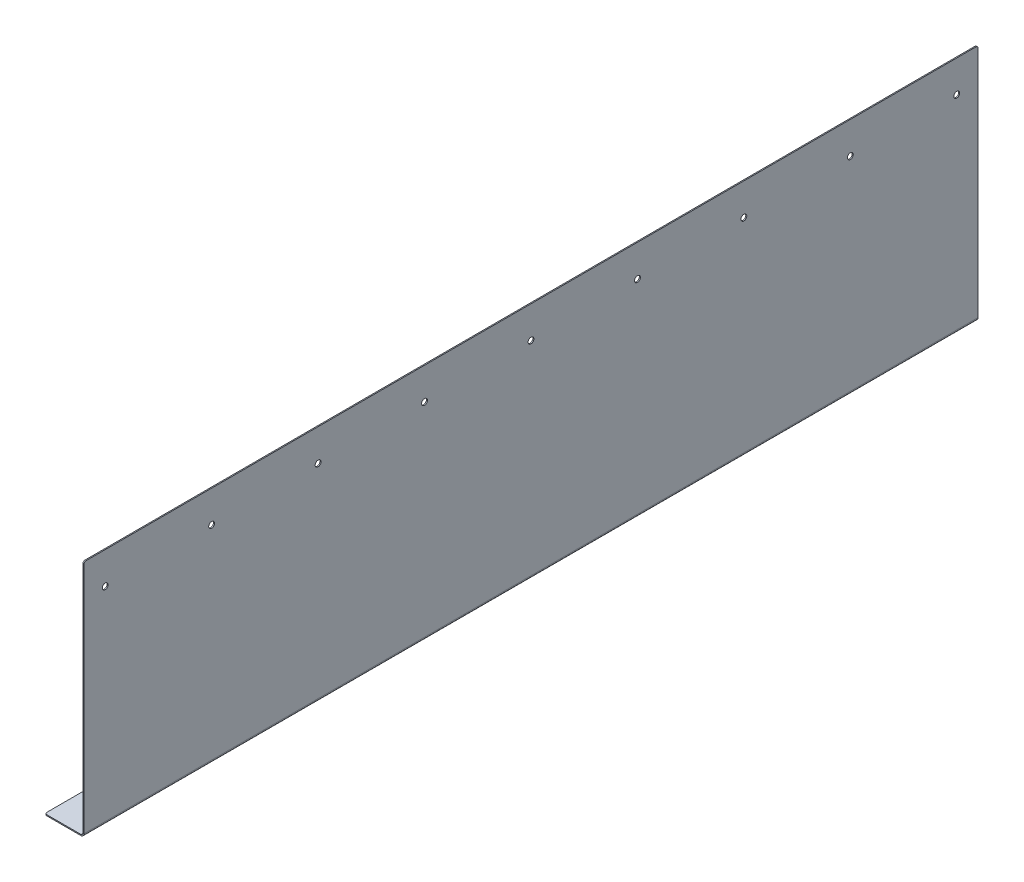
SolidWorks part; units mm, degrees
note: The reader was unsure of these and kept them because the rebuilt part matched: flange length of "Edge-Flange1".
material "3.3547 (EN-AW 5083)"
ref_plane "Front Plane" through (0, 0, 0) normal (0, 0, 1) x (1, 0, 0)
ref_plane "Top Plane" through (0, 0, 0) normal (0, 1, 0) x (1, 0, 0)
ref_plane "Right Plane" through (0, 0, 0) normal (1, 0, 0) x (0, 0, -1)
sketch "Sketch2" plane through (0, 0, 0) normal (0, 0, 1) x (1, 0, 0)
  line L0 (0, 0) -> (0, 225)
  dimension "D1" = 225
base flange "Base-Flange1" sketch "Sketch2" end condition mid plane depth 843 reverse direction no thickness 1 reverse thickness direction no bend radius 2
edge flange "Edge-Flange1" sketch "Sketch5" flange angle 90 flange length 37 flange position material inside bend radius 2 thickness 1 parameters "D6"=10
sketch "Sketch5" plane through (0, 0, 0) normal (0, -1, 0) x (0, 0, 1)
  line L2 (-421.5, 0) -> (-421.5, 36)
  line L3 (-421.5, 36) -> (421.5, 36)
  line L4 (421.5, 36) -> (421.5, 0)
  line L7 (421.5, 0) -> (-421.5, 0) construction
  line L8 (421.5, 0) -> (-421.5, 0)
bend "EdgeBend1" bend radius 2 bend angle 90 parameters "D5"=1
sketch "Sketch9" plane through (0, 0, 0) normal (-1, 0, 0) x (0, 0, 1)
  line L0 (-421.5, 3) -> (-421.5, 225) construction
  line L1 (-421.5, 180) -> (-321.5, 180)
  line L2 (-421.5, 180) -> (-421.5, 150)
  line L3 (-421.5, 150) -> (-321.5, 150)
  line L4 (-321.5, 180) -> (-321.5, 150)
  line L5 (421.5, 225) -> (-421.5, 225) construction
  dimension "D1" = 30
  dimension "D2" = 100
  dimension "D3" = 45
extrude "Cut-Extrude1" [suppressed] cut sketch "Sketch9" against normal up to next
hole_wizard "M5 Clearance Hole1" positions "Sketch6" profile "Sketch8" hole size "M5" standard "DIN" end condition up to next
sketch "Sketch6" plane through (0, 0, 0) normal (-1, 0, 0) x (0, 0, 1)
  line L0 (-401.5, 195) -> (401.5, 195)
  line L2 (0, 0) -> (0, 195) construction
  line L5 (421.5, 225) -> (-421.5, 225) construction
  line L6 (421.5, 3) -> (421.5, 225) construction
  line L8 (-421.5, 3) -> (-421.5, 225) construction
  point P1 (-401.5, 195)
  dimension "D1" = 20
  dimension "D2" = 30
  dimension "D3" = 20
sketch "Sketch8" plane through (0, 195, -401.5) normal (0, 1, 0) x (0, 0, 1)
  line L0 (0, 0) -> (0, 1)
  line L1 (0, 1) -> (2.75, 1)
  line L2 (2.75, 1) -> (2.75, 0.025)
  line L3 (2.75, 0.025) -> (2.775, 0)
  line L5 (2.775, 0) -> (0, 0)
  line L6 (-2.75, 0.025) -> (-2.775, 0) construction
  line L11 (0, -6.35) -> (0, 107.95) construction
  dimension "Thru Hole Dia." = 5.5
  dimension "Thru Hole Depth" = 1
  dimension "Near C'Sink Dia." = 5.55
  dimension "Near C'Sink Angle" = 90
pattern_curve "CrvPattern1" of "M5 Clearance Hole1" parameters "D1"=9, "D3"=10, "D2"=1, "D4"=10
fillet "Fillet1" radius 2 4 edges at (-36, 0.5, 421.5) (-36, 0.5, -421.5) (0.5, 225, 421.5) (0.5, 225, -421.5)
sketch "Bend-Lines1" [suppressed] plane through (0, 0, 0) normal (0, 1, 0) x (1, 0, 0)
sketch "Bounding-Box1" [suppressed] plane through (0, 0, 0) normal (0, 1, 0) x (1, 0, 0)
sheet metal parameters "Sheet-Metal9" thickness 1 parameters "D1"=2
flat pattern "Flat-Pattern9" [suppressed]
sketch "Bend-Lines2" plane through (0, 0, 0) normal (-1, 0, 0) x (0, 0, 1)
sketch3d "Bounding-Box2" [suppressed]
  line L0 (-857, 0, 0) -> (0, 0, 0) construction
  line L1 (-857, 210, 0) -> (0, 210, 0) construction
  line L2 (-857, 0, 0) -> (-857, 210, 0) construction
  line L3 (0, 0, 0) -> (0, 210, 0) construction
sheet metal parameters "Sheet-Metal12" thickness 1 parameters "D1"=2
flat pattern "Flat-Pattern9"
sketch "Bend-Lines2" plane through (0, 0, 0) normal (-1, 0, 0) x (0, 0, 1)
  line L0 (421.5, 1.0365) -> (-421.5, 1.0365) construction
  line L1 (421.5, 1.0365) -> (-421.5, 1.0365) construction
sketch3d "Bounding-Box2" [suppressed]
  line L0 (-843, -34.927, 0) -> (0, -34.927, 0) construction
  line L1 (-843, 225, 0) -> (0, 225, 0) construction
  line L2 (-843, -34.927, 0) -> (-843, 225, 0) construction
  line L3 (0, -34.927, 0) -> (0, 225, 0) construction
bend of the flat pattern "EdgeBend1>1"
sheet metal parameters "Sheet-Metal13" thickness 1 parameters "D1"=2
flat pattern "Flat-Pattern9"
sketch "Bend-Lines2" plane through (0, 0, 0) normal (-1, 0, 0) x (0, 0, 1)
  line L0 (421.5, 1.0365) -> (-421.5, 1.0365) construction
  line L1 (421.5, 1.0365) -> (-421.5, 1.0365) construction
sketch3d "Bounding-Box2" [suppressed]
  line L0 (-843, -34.927, 0) -> (0, -34.927, 0) construction
  line L1 (-843, 225, 0) -> (0, 225, 0) construction
  line L2 (-843, -34.927, 0) -> (-843, 225, 0) construction
  line L3 (0, -34.927, 0) -> (0, 225, 0) construction
bend of the flat pattern "EdgeBend1>1"
sheet metal parameters "Sheet-Metal14" thickness 1 parameters "D1"=2
flat pattern "Flat-Pattern9"
sketch "Bend-Lines2" plane through (0, 0, 0) normal (-1, 0, 0) x (0, 0, 1)
  line L0 (421.5, 1.0365) -> (-421.5, 1.0365) construction
  line L1 (421.5, 1.0365) -> (-421.5, 1.0365) construction
sketch3d "Bounding-Box2" [suppressed]
  line L0 (-842.9999, 225.0005, 0) -> (0, 225, 0) construction
  line L1 (-843, -34.9265, 0) -> (-0.0001, -34.927, 0) construction
  line L2 (-842.9999, 225.0005, 0) -> (-843, -34.9265, 0) construction
  line L3 (0, 225, 0) -> (-0.0001, -34.927, 0) construction
bend of the flat pattern "EdgeBend1>1"
sheet metal parameters "Sheet-Metal15" thickness 1 parameters "D1"=2
flat pattern "Flat-Pattern9"
sketch "Bend-Lines2" plane through (0, 0, 0) normal (-1, 0, 0) x (0, 0, 1)
  line L0 (421.5, 1.0365) -> (-421.5, 1.0365) construction
  line L1 (421.5, 1.0365) -> (-421.5, 1.0365) construction
sketch3d "Bounding-Box2" [suppressed]
  line L0 (-843, -34.927, 0) -> (0, -34.927, 0) construction
  line L1 (-843, 225, 0) -> (0, 225, 0) construction
  line L2 (-843, -34.927, 0) -> (-843, 225, 0) construction
  line L3 (0, -34.927, 0) -> (0, 225, 0) construction
bend of the flat pattern "EdgeBend1>1"
